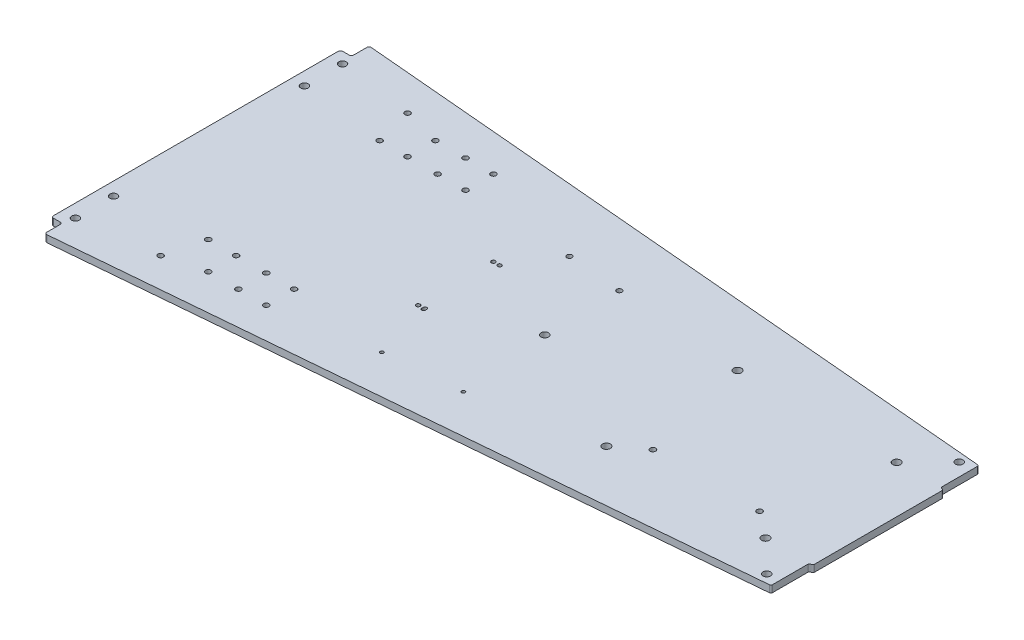
SolidWorks part; units mm, degrees
ref_plane "Front Plane" through (0, 0, 0) normal (0, 0, 1) x (1, 0, 0)
ref_plane "Top Plane" through (0, 0, 0) normal (0, 1, 0) x (1, 0, 0)
ref_plane "Right Plane" through (0, 0, 0) normal (1, 0, 0) x (0, 0, -1)
sketch "Sketch1" plane through (0, 0, 0) normal (0, 1, 0) x (1, 0, 0)
  line L0 (0, -94.3735) -> (0, 94.3735)
  line L1 (0, 94.3735) -> (-621.5262, 148.75)
  line L2 (-621.5262, 148.75) -> (-621.5262, -148.75)
  line L3 (-621.5262, -148.75) -> (0, -94.3735)
  point P7 (0, 0)
  dimension "D1" = 188.747
  dimension "D2" = 297.5
  dimension "D3" = 95
  dimension "D4" = 95
extrude "Boss-Extrude1" add sketch "Sketch1" along normal mid plane 6.35
hole_wizard "M3 Clearance Hole1" positions "Sketch8" profile "Sketch9" hole size "M3" standard "ANSI Metric" end condition through all
sketch "Sketch8" plane through (0, 3.175, 0) normal (0, 1, 0) x (1, 0, 0)
  point P0 (-379.222, 34.29)
  point P3 (-384.81, 34.29)
  point P6 (-384.81, -34.29)
sketch "Sketch9" plane through (-379.222, 3.175, -34.29) normal (1, 0, 0) x (0, 0, 1)
  line L0 (0, 0) -> (0, 6.35)
  line L1 (0, 6.35) -> (1.8, 6.35)
  line L2 (1.8, 6.35) -> (1.8, 0)
  line L5 (1.8, 0) -> (0, 0)
  line L11 (0, -6.35) -> (0, 107.95) construction
  dimension "Thru Hole Dia." = 3.6
  dimension "Thru Hole Depth" = 6.35
hole_wizard "1/4 Clearance Hole1" positions "Sketch10" profile "Sketch11" hole size "1/4" standard "ANSI Inch" end condition through all
sketch "Sketch10" plane through (0, 3.175, 0) normal (0, 1, 0) x (1, 0, 0)
  point P0 (-187.8373, 59.7527)
  point P3 (-42.9319, 59.7527)
  point P6 (-42.9319, -59.7527)
  point P9 (-187.8373, -59.7527)
  point P12 (0, 0)
  point P13 (0, 0)
sketch "Sketch11" plane through (-187.8373, 3.175, -59.7527) normal (1, 0, 0) x (0, 0, 1)
  line L0 (0, 0) -> (0, 6.35)
  line L1 (0, 6.35) -> (3.5712, 6.35)
  line L2 (3.5712, 6.35) -> (3.5712, 0)
  line L5 (3.5712, 0) -> (0, 0)
  line L11 (0, -6.35) -> (0, 107.95) construction
  dimension "Thru Hole Dia." = 7.1425
  dimension "Thru Hole Depth" = 6.35
sketch "Sketch12" plane through (0, 3.175, 0) normal (0, 1, 0) x (1, 0, 0)
  line L0 (-380.8412, -33.6169) -> (-380.8412, -34.0868) construction
  line L1 (-380.8412, -34.4932) -> (-380.8412, -34.9631) construction
  line L2 (-377.6027, -34.9631) -> (-377.6027, -34.4932) construction
  line L3 (-377.6027, -34.0868) -> (-377.6027, -33.6169) construction
  line L4 (-380.8412, -33.6169) -> (-380.8412, -34.0868)
  line L5 (-380.8412, -34.4932) -> (-380.8412, -34.9631)
  line L6 (-377.6027, -34.9631) -> (-377.6027, -34.4932)
  line L7 (-377.6027, -34.0868) -> (-377.6027, -33.6169)
  arc A0 (-380.8412, -34.0868) -> (-380.8412, -34.4932) centre (-379.222, -34.29) ccw construction
  arc A1 (-380.8412, -34.9631) -> (-377.6027, -34.9631) centre (-379.222, -34.9631) ccw construction
  arc A2 (-377.6027, -34.4932) -> (-377.6027, -34.0868) centre (-379.222, -34.29) ccw construction
  arc A3 (-377.6027, -33.6169) -> (-380.8412, -33.6169) centre (-379.222, -33.6169) ccw construction
  arc A4 (-380.8412, -34.0868) -> (-380.8412, -34.4932) centre (-379.222, -34.29) ccw
  arc A5 (-380.8412, -34.9631) -> (-377.6027, -34.9631) centre (-379.222, -34.9631) ccw
  arc A6 (-377.6027, -34.4932) -> (-377.6027, -34.0868) centre (-379.222, -34.29) ccw
  arc A7 (-377.6027, -33.6169) -> (-380.8412, -33.6169) centre (-379.222, -33.6169) ccw
extrude "Cut-Extrude1" cut sketch "Sketch12" against normal through all
hole_wizard "#8 Clearance Hole1" positions "Sketch13" profile "Sketch14" hole size "#8" standard "ANSI Inch" end condition through all
sketch "Sketch13" plane through (0, 3.175, 0) normal (0, 1, 0) x (1, 0, 0)
  point P0 (-506.818, -78.0643)
  point P3 (-506.818, -103.4643)
  point P6 (-541.1982, -112.4445)
  point P9 (-532.218, -78.0643)
  point P12 (-479.3927, -78.0643)
  point P15 (-479.3927, -103.4643)
  point P18 (-453.9927, -78.0643)
  point P21 (-453.9927, -103.4643)
  point P24 (-453.9927, 78.0643)
  point P27 (-453.9927, 103.4643)
  point P30 (-479.3927, 78.0643)
  point P33 (-479.3927, 103.4643)
  point P36 (-541.1982, 112.4445)
  point P39 (-532.218, 78.0643)
  point P42 (-506.818, 103.4643)
  point P45 (-506.818, 78.0643)
sketch "Sketch14" plane through (-506.818, 3.175, 78.0643) normal (1, 0, 0) x (0, 0, 1)
  line L0 (0, 0) -> (0, 6.35)
  line L1 (0, 6.35) -> (2.4574, 6.35)
  line L2 (2.4574, 6.35) -> (2.4574, 0)
  line L5 (2.4574, 0) -> (0, 0)
  line L11 (0, -6.35) -> (0, 107.95) construction
  dimension "Thru Hole Dia." = 4.9149
  dimension "Thru Hole Depth" = 6.35
sketch "Sketch15" plane through (0, 3.175, 0) normal (0, 1, 0) x (1, 0, 0)
  circle A0 centre (-295.9182, -81.917) radius 1.55 construction
  circle A1 centre (-364.1575, -87.8871) radius 1.55 construction
  circle A6 centre (-295.9182, -81.917) radius 1.55
  circle A7 centre (-364.1575, -87.8871) radius 1.55
extrude "Cut-Extrude2" cut sketch "Sketch15" against normal through all
sketch "Sketch16" plane through (0, 3.175, 0) normal (0, 1, 0) x (1, 0, 0)
  circle A0 centre (-609.6, -121.6503) radius 3.3782 construction
  circle A1 centre (-609.6, -86.9431) radius 3.3782 construction
  circle A2 centre (-609.6, 86.9431) radius 3.3782 construction
  circle A3 centre (-609.6, 121.6503) radius 3.3782 construction
  circle A4 centre (-609.6, -121.6503) radius 3.3782
  circle A5 centre (-609.6, -86.9431) radius 3.3782
  circle A6 centre (-609.6, 86.9431) radius 3.3782
  circle A7 centre (-609.6, 121.6503) radius 3.3782
extrude "Cut-Extrude3" cut sketch "Sketch16" against normal through all
fillet "Fillet1" radius 1 2 edges at (-621.5262, 0, 148.75) (-621.5262, 0, -148.75)
sketch "Sketch17" plane through (0, 3.175, 0) normal (0, 1, 0) x (1, 0, 0)
  line L0 (-3, 94.636) -> (-3, 59.636)
  line L1 (0, 94.3735) -> (-620.4391, 148.6549) construction
  line L2 (-3, 59.636) -> (0, 59.636)
  line L3 (0, -94.3735) -> (0, 94.3735) construction
  line L4 (0, 59.636) -> (0, 94.3735)
  line L5 (0, 94.3735) -> (-3, 94.636)
  dimension "D1" = 3
  dimension "D2" = 35
extrude "Cut-Extrude4" cut sketch "Sketch17" against normal through all
mirror "Mirror1" about plane through (0, 0, 0) normal (0, 0, 1) of "Cut-Extrude4"
fillet "Fillet2" radius 1.5 6 edges at (0, 0, -59.636) (-3, 0, -59.636) (-3, 0, -94.636) (0, 0, 59.636) (-3, 0, 59.636) (-3, 0, 94.636)
hole_wizard "#13 (0.185) Diameter Hole1" positions "Sketch18" profile "Sketch20" hole size "#13" standard "ANSI Inch" end condition through all
sketch "Sketch18" plane through (0, 3.175, 0) normal (0, 1, 0) x (1, 0, 0)
  point P0 (-354.4456, 73.1877)
  point P3 (-304.6358, 68.83)
sketch "Sketch20" plane through (-354.4456, 3.175, -73.1877) normal (1, 0, 0) x (0, 0, 1)
  line L0 (0, 0) -> (0, 6.35)
  line L1 (0, 6.35) -> (2.3495, 6.35)
  line L2 (2.3495, 6.35) -> (2.3495, 0)
  line L5 (2.3495, 0) -> (0, 0)
  line L11 (0, -6.35) -> (0, 107.95) construction
  dimension "Thru Hole Dia." = 4.699
  dimension "Thru Hole Depth" = 6.35
hole_wizard "1/4 Clearance Hole2" positions "Sketch21" profile "Sketch22" hole size "1/4" standard "ANSI Inch" end condition through all
sketch "Sketch21" plane through (0, 3.175, 0) normal (0, 1, 0) x (1, 0, 0)
  point P0 (-14.732, 88.4699)
  point P3 (-14.0462, -87.4539)
  point P6 (-303.7332, 0)
sketch "Sketch22" plane through (-14.732, 3.175, -88.4699) normal (1, 0, 0) x (0, 0, 1)
  line L0 (0, 0) -> (0, 6.35)
  line L1 (0, 6.35) -> (3.3782, 6.35)
  line L2 (3.3782, 6.35) -> (3.3782, 0)
  line L5 (3.3782, 0) -> (0, 0)
  line L11 (0, -6.35) -> (0, 107.95) construction
  dimension "Thru Hole Dia." = 6.7564
  dimension "Thru Hole Depth" = 6.35
sketch "Sketch23" plane through (0, 3.175, 0) normal (0, 1, 0) x (1, 0, 0)
  line L0 (-621.5262, 147.6587) -> (-621.5262, -147.6587) construction
  line L1 (-621.5262, 131.6587) -> (-611.5262, 131.6587)
  line L2 (-621.5262, 131.6587) -> (-621.5262, 148.6587)
  line L3 (-621.5262, 148.6587) -> (-611.5262, 148.6587)
  line L4 (-611.5262, 131.6587) -> (-611.5262, 148.6587)
  line L5 (0, 0) -> (-621.5262, 0) construction
  line L6 (-611.5262, -131.6587) -> (-611.5262, -148.6587)
  line L7 (-621.5262, -148.6587) -> (-611.5262, -148.6587)
  line L8 (-621.5262, -131.6587) -> (-621.5262, -148.6587)
  line L9 (-621.5262, -131.6587) -> (-611.5262, -131.6587)
  arc A0 (-620.4391, 148.6549) -> (-621.5262, 147.6587) centre (-620.5262, 147.6587) ccw construction
  dimension "D1" = 10
  dimension "D2" = 17
extrude "Cut-Extrude5" cut sketch "Sketch23" against normal through all
fillet "Fillet3" radius 2 6 edges at (-621.5262, 0, -131.6587) (-611.5262, 0, -131.6587) (-611.5262, 0, -147.8751) (-611.5262, 0, 147.8751) (-611.5262, 0, 131.6587) (-621.5262, 0, 131.6587)
hole_wizard "Ø5.0mm Dowel Hole1" positions "Sketch24" profile "Sketch25" hole size "Ø5.0" standard "ANSI Metric" end condition through all
sketch "Sketch24" plane through (0, 3.175, 0) normal (0, 1, 0) x (1, 0, 0)
  point P0 (-163.9621, -41.275)
  point P3 (-66.8071, -41.275)
sketch "Sketch25" plane through (-163.9621, 3.175, 41.275) normal (1, 0, 0) x (0, 0, 1)
  line L0 (0, 0) -> (0, 6.35)
  line L1 (0, 6.35) -> (2.5, 6.35)
  line L2 (2.5, 6.35) -> (2.5, 0)
  line L5 (2.5, 0) -> (0, 0)
  line L11 (0, -6.35) -> (0, 107.95) construction
  dimension "Thru Hole Dia." = 5
  dimension "Thru Hole Depth" = 6.35
